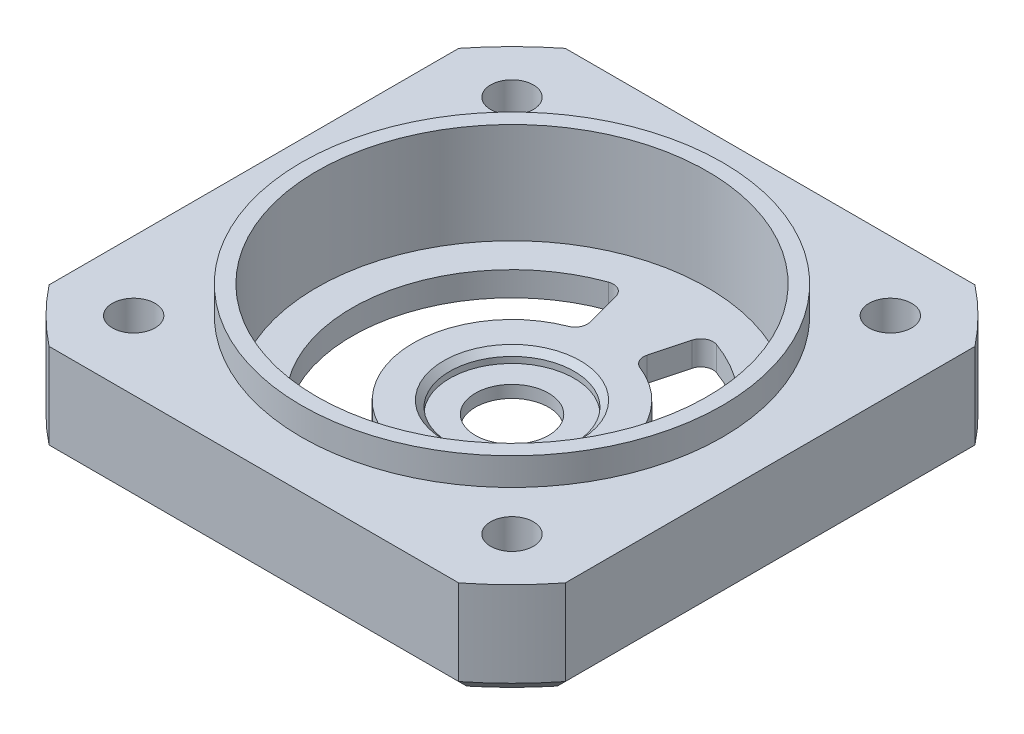
SolidWorks part; units mm, degrees
ref_plane "Front Plane" through (0, 0, 0) normal (0, 0, 1) x (1, 0, 0)
ref_plane "Top Plane" through (0, 0, 0) normal (0, 1, 0) x (1, 0, 0)
ref_plane "Right Plane" through (0, 0, 0) normal (1, 0, 0) x (0, 0, -1)
sketch "Sketch2" plane through (0, 0, 0) normal (0, 1, 0) x (1, 0, 0)
  line L1 (-21.15, 21.15) -> (21.15, 21.15)
  line L2 (-21.15, 21.15) -> (-21.15, -21.15)
  line L3 (-21.15, -21.15) -> (21.15, -21.15)
  line L4 (21.15, 21.15) -> (21.15, -21.15)
  line L5 (-21.15, 21.15) -> (21.15, -21.15) construction
  line L6 (-21.15, -21.15) -> (21.15, 21.15) construction
  point P0 (0, 0)
  dimension "D1" = 42.3
extrude "Boss-Extrude1" add sketch "Sketch2" along normal blind 8
sketch "Sketch5" plane through (0, 8, 0) normal (0, 1, 0) x (1, 0, 0)
  circle A0 centre (0, 0) radius 27
  circle A1 centre (0, 0) radius 29.9106
  dimension "D1" = 54
extrude "Cut-Extrude4" cut sketch "Sketch5" against normal through all
sketch "Sketch6" plane through (0, 8, 0) normal (0, 1, 0) x (1, 0, 0)
  circle A2 centre (0, 0) radius 16
  circle A3 centre (0, 0) radius 10 construction
  dimension "D1" = 32
  dimension "D5" = 20
extrude "Cut-Extrude7" cut sketch "Sketch6" against normal offset from surface (7 mm away) 1 up to face at (0, 0, 0)
sketch "Sketch8" plane through (0, 1, 0) normal (0, 1, 0) x (1, 0, 0)
  circle A0 centre (0, 0) radius 5.1
  circle A2 centre (0, 0) radius 16
  circle A3 centre (0, 0) radius 16
  dimension "D1" = 10.2
  dimension "D2" = 0
extrude "Boss-Extrude3" add sketch "Sketch8" along normal blind 1
sketch "Sketch9" plane through (0, 2, 0) normal (0, 1, 0) x (1, 0, 0)
  line L0 (3.3905, 12.6536) -> (2.0964, 7.824)
  line L1 (3.3905, -12.6536) -> (2.0964, -7.824)
  line L2 (2.0964, -7.824) -> (0, 0) construction
  line L3 (2.0964, 7.824) -> (0, 0) construction
  line L4 (-21.15, 16.7833) -> (-21.15, -16.7833) construction
  line L5 (0, -4.4) -> (0, 4.4) construction
  line L6 (-2.0964, 7.824) -> (0, 0) construction
  line L7 (-2.0964, -7.824) -> (0, 0) construction
  line L8 (-3.3905, -12.6536) -> (-2.0964, -7.824)
  line L9 (-3.3905, 12.6536) -> (-2.0964, 7.824)
  arc A0 (3.3905, 12.6536) -> (3.3905, -12.6536) centre (0, 0) cw
  circle A1 centre (0, 0) radius 5.1 construction
  arc A2 (2.0964, 7.824) -> (2.0964, -7.824) centre (0, 0) cw
  arc A3 (-2.0964, 7.824) -> (-2.0964, -7.824) centre (0, 0) ccw
  arc A4 (-3.3905, 12.6536) -> (-3.3905, -12.6536) centre (0, 0) ccw
  dimension "D1" = 15
  dimension "D4" = 3
  dimension "D2" = 15
  dimension "D3" = 5
extrude "Cut-Extrude8" cut sketch "Sketch9" against normal through all
fillet "Fillet1" radius 1 8 edges at (-3.3905, 1, 12.6536) (-2.0964, 1, -7.824) (-2.0964, 1, 7.824) (-3.3905, 1, -12.6536) (2.0964, 1, 7.824) (2.0964, 1, -7.824) (3.3905, 1, 12.6536) (3.3905, 1, -12.6536)
sketch "Sketch10" plane through (0, 1, 0) normal (0, 1, 0) x (1, 0, 0)
  circle A0 centre (0, 0) radius 3
  dimension "D1" = 6
extrude "Cut-Extrude9" cut sketch "Sketch10" against normal through all
sketch "Sketch7" plane through (0, 8, 0) normal (0, 1, 0) x (1, 0, 0)
  line L1 (-15.5, 15.5) -> (15.5, 15.5) construction
  line L2 (-15.5, 15.5) -> (-15.5, -15.5) construction
  line L3 (-15.5, -15.5) -> (15.5, -15.5) construction
  line L4 (15.5, 15.5) -> (15.5, -15.5) construction
  line L5 (-15.5, 15.5) -> (15.5, -15.5) construction
  line L6 (-15.5, -15.5) -> (15.5, 15.5) construction
  circle A0 centre (-15.5, 15.5) radius 1.75
  circle A1 centre (15.5, 15.5) radius 1.75
  circle A2 centre (15.5, -15.5) radius 1.75
  circle A3 centre (-15.5, -15.5) radius 1.75
  point P0 (0, 0)
  point P16 (0, 0)
  dimension "D3" = 3.5
  dimension "D1" = 31
  dimension "D2" = 31
  dimension "D4" = 4
extrude "Cut-Extrude6" cut sketch "Sketch7" against normal through all
chamfer "Chamfer4" distance 1 angle 45 8 edges at (19.0919, 0, 19.0919) (0, 0, 21.15) (-19.0919, 0, 19.0919) (-21.15, 0, 0) (-19.0919, 0, -19.0919) (0, 0, -21.15) (19.0919, 0, -19.0919) (21.15, 0, 0)
chamfer "Chamfer5" distance 2 angle 45 4 edges at (-15.5, 0, -13.75) (15.5, 0, -13.75) (15.5, 0, 17.25) (-15.5, 0, 17.25)
chamfer "Chamfer6" distance 0.5 angle 45 1 edges at (0, 2, 5.1)
sketch "Sketch11" plane through (0, 8, 0) normal (0, 1, 0) x (1, 0, 0)
  circle A1 centre (0, 0) radius 16 construction
  circle A2 centre (0, 0) radius 16
  circle A3 centre (0, 0) radius 17.25
  point P0 (16.5814, -3.9464)
  dimension "D1" = 1.25
extrude "Boss-Extrude4" add sketch "Sketch11" along normal blind 2.25
